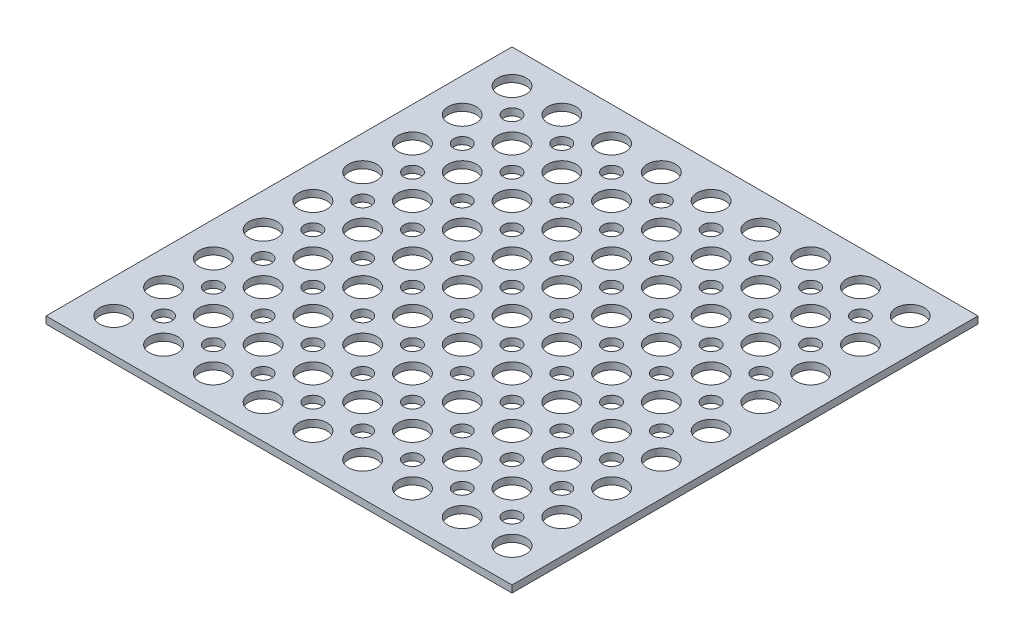
SolidWorks part; units mm, degrees
material "ABS"
ref_plane "Front Plane" through (0, 0, 0) normal (0, 0, 1) x (1, 0, 0)
ref_plane "Top Plane" through (0, 0, 0) normal (0, 1, 0) x (1, 0, 0)
ref_plane "Right Plane" through (0, 0, 0) normal (1, 0, 0) x (0, 0, -1)
sketch "Sketch1" plane through (0, 0, 0) normal (0, 1, 0) x (1, 0, 0)
  line L1 (0, 0) -> (165, 0)
  line L2 (0, 0) -> (0, 165)
  line L3 (0, 165) -> (165, 165)
  line L4 (165, 0) -> (165, 165)
  dimension "D1" = 165
  dimension "D2" = 165
extrude "Boss-Extrude1" add sketch "Sketch1" along normal blind 2.5
sketch "Sketch2" plane through (0, 2.5, 0) normal (0, 1, 0) x (1, 0, 0)
  line L0 (135.375, 153) -> (153, 135.375) construction
  line L7 (12, 29.625) -> (29.625, 12) construction
  line L8 (165, 0) -> (165, 165) construction
  line L9 (12, 153) -> (153, 153) construction
  line L10 (12, 153) -> (12, 12) construction
  line L11 (12, 12) -> (153, 12) construction
  line L12 (153, 153) -> (153, 12) construction
  line L13 (0, 0) -> (165, 0) construction
  line L14 (0, 165) -> (0, 0) construction
  line L15 (165, 165) -> (0, 165) construction
  line L16 (12, 153) -> (153, 12) construction
  line L17 (12, 12) -> (153, 153) construction
  line L18 (12, 135.375) -> (29.625, 153) construction
  circle A0 centre (12, 153) radius 5
  circle A1 centre (29.625, 153) radius 5
  circle A2 centre (47.25, 153) radius 5
  circle A3 centre (64.875, 153) radius 5
  circle A4 centre (82.5, 153) radius 5
  circle A5 centre (100.125, 153) radius 5
  circle A6 centre (117.75, 153) radius 5
  circle A7 centre (135.375, 153) radius 5
  circle A8 centre (153, 153) radius 5
  circle A9 centre (29.625, 135.375) radius 5
  circle A10 centre (47.25, 135.375) radius 5
  circle A11 centre (64.875, 135.375) radius 5
  circle A12 centre (82.5, 135.375) radius 5
  circle A13 centre (100.125, 135.375) radius 5
  circle A14 centre (117.75, 135.375) radius 5
  circle A15 centre (135.375, 135.375) radius 5
  circle A16 centre (153, 135.375) radius 5
  circle A17 centre (29.625, 117.75) radius 5
  circle A18 centre (47.25, 117.75) radius 5
  circle A19 centre (64.875, 117.75) radius 5
  circle A20 centre (82.5, 117.75) radius 5
  circle A21 centre (100.125, 117.75) radius 5
  circle A22 centre (117.75, 117.75) radius 5
  circle A23 centre (135.375, 117.75) radius 5
  circle A24 centre (153, 117.75) radius 5
  circle A25 centre (29.625, 100.125) radius 5
  circle A26 centre (47.25, 100.125) radius 5
  circle A27 centre (64.875, 100.125) radius 5
  circle A28 centre (82.5, 100.125) radius 5
  circle A29 centre (100.125, 100.125) radius 5
  circle A30 centre (117.75, 100.125) radius 5
  circle A31 centre (135.375, 100.125) radius 5
  circle A32 centre (153, 100.125) radius 5
  circle A33 centre (29.625, 82.5) radius 5
  circle A34 centre (47.25, 82.5) radius 5
  circle A35 centre (64.875, 82.5) radius 5
  circle A36 centre (82.5, 82.5) radius 5
  circle A37 centre (100.125, 82.5) radius 5
  circle A38 centre (117.75, 82.5) radius 5
  circle A39 centre (135.375, 82.5) radius 5
  circle A40 centre (153, 82.5) radius 5
  circle A41 centre (29.625, 64.875) radius 5
  circle A42 centre (47.25, 64.875) radius 5
  circle A43 centre (64.875, 64.875) radius 5
  circle A44 centre (82.5, 64.875) radius 5
  circle A45 centre (100.125, 64.875) radius 5
  circle A46 centre (117.75, 64.875) radius 5
  circle A47 centre (135.375, 64.875) radius 5
  circle A48 centre (153, 64.875) radius 5
  circle A49 centre (29.625, 47.25) radius 5
  circle A50 centre (47.25, 47.25) radius 5
  circle A51 centre (64.875, 47.25) radius 5
  circle A52 centre (82.5, 47.25) radius 5
  circle A53 centre (100.125, 47.25) radius 5
  circle A54 centre (117.75, 47.25) radius 5
  circle A55 centre (135.375, 47.25) radius 5
  circle A56 centre (153, 47.25) radius 5
  circle A57 centre (29.625, 29.625) radius 5
  circle A58 centre (47.25, 29.625) radius 5
  circle A59 centre (64.875, 29.625) radius 5
  circle A60 centre (82.5, 29.625) radius 5
  circle A61 centre (100.125, 29.625) radius 5
  circle A62 centre (117.75, 29.625) radius 5
  circle A63 centre (135.375, 29.625) radius 5
  circle A64 centre (153, 29.625) radius 5
  circle A65 centre (29.625, 12) radius 5
  circle A66 centre (47.25, 12) radius 5
  circle A67 centre (64.875, 12) radius 5
  circle A68 centre (82.5, 12) radius 5
  circle A69 centre (100.125, 12) radius 5
  circle A70 centre (117.75, 12) radius 5
  circle A71 centre (135.375, 12) radius 5
  circle A72 centre (153, 12) radius 5
  circle A73 centre (12, 135.375) radius 5
  circle A74 centre (12, 117.75) radius 5
  circle A75 centre (12, 100.125) radius 5
  circle A76 centre (12, 82.5) radius 5
  circle A77 centre (12, 64.875) radius 5
  circle A78 centre (12, 47.25) radius 5
  circle A79 centre (12, 29.625) radius 5
  circle A80 centre (12, 12) radius 5
  circle A81 centre (20.8125, 144.1875) radius 3
  circle A82 centre (38.4375, 144.1875) radius 3
  circle A83 centre (56.0625, 144.1875) radius 3
  circle A84 centre (73.6875, 144.1875) radius 3
  circle A85 centre (91.3125, 144.1875) radius 3
  circle A86 centre (108.9375, 144.1875) radius 3
  circle A87 centre (126.5625, 144.1875) radius 3
  circle A88 centre (144.1875, 144.1875) radius 3
  circle A89 centre (38.4375, 126.5625) radius 3
  circle A90 centre (56.0625, 126.5625) radius 3
  circle A91 centre (73.6875, 126.5625) radius 3
  circle A92 centre (91.3125, 126.5625) radius 3
  circle A93 centre (108.9375, 126.5625) radius 3
  circle A94 centre (126.5625, 126.5625) radius 3
  circle A95 centre (144.1875, 126.5625) radius 3
  circle A96 centre (38.4375, 108.9375) radius 3
  circle A97 centre (56.0625, 108.9375) radius 3
  circle A98 centre (73.6875, 108.9375) radius 3
  circle A99 centre (91.3125, 108.9375) radius 3
  circle A100 centre (108.9375, 108.9375) radius 3
  circle A101 centre (126.5625, 108.9375) radius 3
  circle A102 centre (144.1875, 108.9375) radius 3
  circle A103 centre (38.4375, 91.3125) radius 3
  circle A104 centre (56.0625, 91.3125) radius 3
  circle A105 centre (73.6875, 91.3125) radius 3
  circle A106 centre (91.3125, 91.3125) radius 3
  circle A107 centre (108.9375, 91.3125) radius 3
  circle A108 centre (126.5625, 91.3125) radius 3
  circle A109 centre (144.1875, 91.3125) radius 3
  circle A110 centre (38.4375, 73.6875) radius 3
  circle A111 centre (56.0625, 73.6875) radius 3
  circle A112 centre (73.6875, 73.6875) radius 3
  circle A113 centre (91.3125, 73.6875) radius 3
  circle A114 centre (108.9375, 73.6875) radius 3
  circle A115 centre (126.5625, 73.6875) radius 3
  circle A116 centre (144.1875, 73.6875) radius 3
  circle A117 centre (38.4375, 56.0625) radius 3
  circle A118 centre (56.0625, 56.0625) radius 3
  circle A119 centre (73.6875, 56.0625) radius 3
  circle A120 centre (91.3125, 56.0625) radius 3
  circle A121 centre (108.9375, 56.0625) radius 3
  circle A122 centre (126.5625, 56.0625) radius 3
  circle A123 centre (144.1875, 56.0625) radius 3
  circle A124 centre (38.4375, 38.4375) radius 3
  circle A125 centre (56.0625, 38.4375) radius 3
  circle A126 centre (73.6875, 38.4375) radius 3
  circle A127 centre (91.3125, 38.4375) radius 3
  circle A128 centre (108.9375, 38.4375) radius 3
  circle A129 centre (126.5625, 38.4375) radius 3
  circle A130 centre (144.1875, 38.4375) radius 3
  circle A131 centre (38.4375, 20.8125) radius 3
  circle A132 centre (56.0625, 20.8125) radius 3
  circle A133 centre (73.6875, 20.8125) radius 3
  circle A134 centre (91.3125, 20.8125) radius 3
  circle A135 centre (108.9375, 20.8125) radius 3
  circle A136 centre (126.5625, 20.8125) radius 3
  circle A137 centre (144.1875, 20.8125) radius 3
  circle A138 centre (20.8125, 126.5625) radius 3
  circle A139 centre (20.8125, 108.9375) radius 3
  circle A140 centre (20.8125, 91.3125) radius 3
  circle A141 centre (20.8125, 73.6875) radius 3
  circle A142 centre (20.8125, 56.0625) radius 3
  circle A143 centre (20.8125, 38.4375) radius 3
  circle A144 centre (20.8125, 20.8125) radius 3
  dimension "D1" = 12
  dimension "D3" = 10
  dimension "D8" = 6
  dimension "D2" = 12
  dimension "D4" = 12
  dimension "D5" = 12
  dimension "D6" = 9
  dimension "D9" = 8
  dimension "D7" = 9
  dimension "D10" = 8
extrude "Cut-Extrude1" cut sketch "Sketch2" against normal blind 2.5
